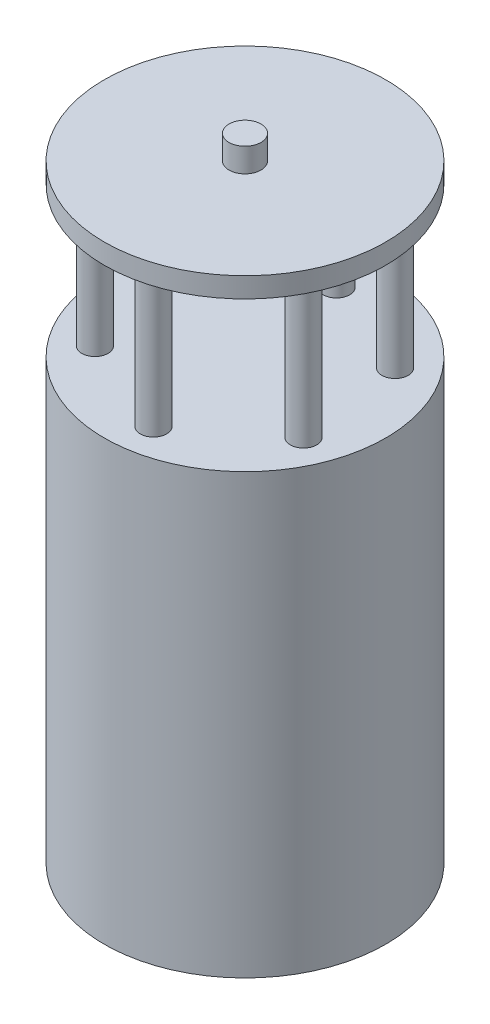
SolidWorks part; units mm, degrees
ref_plane "Front Plane" through (0, 0, 0) normal (0, 0, 1) x (1, 0, 0)
ref_plane "Top Plane" through (0, 0, 0) normal (0, 1, 0) x (1, 0, 0)
ref_plane "Right Plane" through (0, 0, 0) normal (1, 0, 0) x (0, 0, -1)
sketch "Sketch1" plane through (0, 0, 0) normal (0, 1, 0) x (1, 0, 0)
  circle A0 centre (0, 0) radius 27.955
  dimension "D1" = 55.91
extrude "Boss-Extrude1" add sketch "Sketch1" along normal blind 4
sketch "Sketch2" plane through (0, 4, 0) normal (0, 1, 0) x (1, 0, 0)
  circle A0 centre (0, 0) radius 3.175
  dimension "D1" = 6.35
extrude "Boss-Extrude2" add sketch "Sketch2" along normal blind 4.76
sketch "Sketch3" plane through (0, 0, 0) normal (0, -1, 0) x (1, 0, 0)
  circle A0 centre (0, 0) radius 21.2558
  circle A1 centre (2.874, 21.0606) radius 2.6153
  circle A2 centre (19.6761, 8.0413) radius 2.6153
  circle A3 centre (16.802, -13.0193) radius 2.6153
  circle A4 centre (-2.874, -21.0606) radius 2.6153
  circle A5 centre (-19.6761, -8.0413) radius 2.6153
  circle A6 centre (-16.802, 13.0193) radius 2.6153
  point P17 (0, 0)
  dimension "D1" = 6
extrude "Boss-Extrude3" add sketch "Sketch3" along normal blind 29.718 contours A0 A4 | A0 A4 | A0 A3 | A0 A3 | A0 A2 | A0 A2 | A0 A1 | A0 A1 | A0 A6 | A0 A6 | A0 A5 | A0 A5 region at (18.6222, 0, 7.6106) region at (20.6763, 0, 8.4501) region at (17.6561, 0, -13.6811) region at (15.9021, 0, -12.322) region at (2.7201, 0, 19.9327) region at (3.0201, 0, 22.1312) region at (-3.0201, 0, -22.1312) region at (-2.7201, 0, -19.9327) region at (-15.9021, 0, 12.322) region at (-17.6561, 0, 13.6811) region at (-20.6763, 0, -8.4501) region at (-18.6222, 0, -7.6106)
sketch "Sketch4" plane through (0, -29.718, 0) normal (0, -1, 0) x (1, 0, 0)
  circle A0 centre (0, 0) radius 27.955
extrude "Boss-Extrude4" add sketch "Sketch4" along normal blind 87.122
sketch "Sketch5" plane through (0, -116.84, 0) normal (0, -1, 0) x (1, 0, 0)
  circle A0 centre (0, 0) radius 22.7587
extrude "Cut-Extrude1" cut sketch "Sketch5" against normal blind 80
